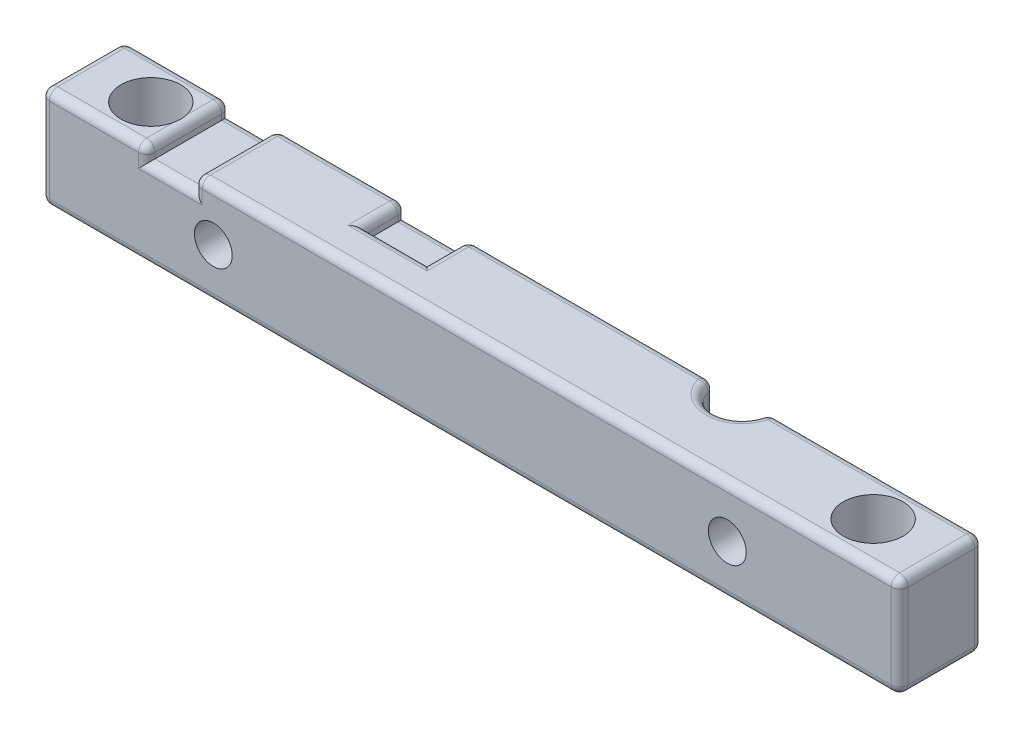
SolidWorks part; units mm, degrees
ref_plane "Front Plane" through (0, 0, 0) normal (0, 0, 1) x (1, 0, 0)
ref_plane "Top Plane" through (0, 0, 0) normal (0, 1, 0) x (1, 0, 0)
ref_plane "Right Plane" through (0, 0, 0) normal (1, 0, 0) x (0, 0, -1)
sketch "Sketch2" plane through (0, 0, 0) normal (0, 1, 0) x (1, 0, 0)
  line L0 (39.243, 7.62) -> (39.243, 0) construction
  line L1 (0, 7.62) -> (78.486, 7.62)
  line L2 (0, 7.62) -> (0, 0)
  line L3 (0, 0) -> (78.486, 0)
  line L4 (78.486, 7.62) -> (78.486, 0)
  line L5 (6.223, 3.81) -> (72.263, 3.81) construction
  circle A0 centre (6.223, 3.81) radius 2.7305
  circle A1 centre (72.263, 3.81) radius 2.7305
  point P10 (39.243, 3.81)
  dimension "D4" = 5.461
  dimension "D1" = 7.62
  dimension "D2" = 78.486
  dimension "D3" = 66.04
extrude "Boss-Extrude1" add sketch "Sketch2" along normal blind 9.271
sketch "Sketch3" plane through (0, 0, 0) normal (0, 0, 1) x (1, 0, 0)
  line L0 (39.243, 9.271) -> (39.243, 0) construction
  line L1 (15.748, 4.6355) -> (62.738, 4.6355) construction
  line L2 (0, 9.271) -> (78.486, 9.271) construction
  line L3 (0, 0) -> (78.486, 0) construction
  circle A0 centre (15.748, 4.6355) radius 1.7272
  circle A1 centre (62.738, 4.6355) radius 1.7272
  point P8 (39.243, 4.6355)
  dimension "D1" = 3.4544
  dimension "D2" = 46.99
extrude "Cut-Extrude1" cut sketch "Sketch3" against normal up to surface (7.62 mm away) up to face at (39.243, 4.6355, -7.62)
sketch "Sketch4" plane through (0, 0, 0) normal (0, -1, 0) x (1, 0, 0)
  line L0 (58.928, -7.7089) -> (53.848, -7.7089)
  line L1 (72.263, -3.81) -> (56.388, -3.81) construction
  line L2 (56.388, -3.81) -> (56.388, -7.7089) construction
  line L3 (78.486, -7.62) -> (0, -7.62) construction
  arc A0 (58.928, -7.7089) -> (53.848, -7.7089) centre (56.388, -7.7089) ccw
  circle A1 centre (72.263, -3.81) radius 2.7305 construction
  dimension "D3" = 2.54
  dimension "D1" = 15.875
  dimension "D2" = 3.8989
extrude "Cut-Extrude2" cut sketch "Sketch4" against normal up to surface (9.271 mm away) up to face at (6.223, 9.271, -1.0795)
sketch "Sketch5" plane through (0, 9.271, 0) normal (0, 1, 0) x (1, 0, 0)
  line L0 (53.8496, 7.62) -> (0, 7.62) construction
  line L1 (13.97, 0) -> (9.652, 0)
  line L2 (13.97, 0) -> (13.97, 7.62)
  line L3 (13.97, 7.62) -> (9.652, 7.62)
  line L4 (9.652, 0) -> (9.652, 7.62)
  line L5 (0, 0) -> (78.486, 0) construction
  line L6 (0, 7.62) -> (0, 0) construction
  line L7 (25.7505, 5.715) -> (28.608, 5.715) construction
  line L8 (25.7505, 7.62) -> (31.4655, 7.62)
  line L9 (25.7505, 7.62) -> (25.7505, 3.81)
  line L10 (25.7505, 3.81) -> (31.4655, 3.81)
  line L11 (31.4655, 7.62) -> (31.4655, 3.81)
  line L12 (28.608, 5.715) -> (28.608, 7.62) construction
  circle A0 centre (6.223, 3.81) radius 2.7305 construction
  dimension "D1" = 3.429
  dimension "D2" = 4.318
  dimension "D3" = 22.385
  dimension "D4" = 5.715
  dimension "D5" = 3.81
extrude "Cut-Extrude3" cut sketch "Sketch5" against normal blind 1.27
fillet "Fillet1" radius 0.762 35 edges at (0, 4.6355, -7.62) (0, 4.6355, 0) (0, 0, -3.81) (26.9248, 0, -7.62) (68.7062, 0, -7.62) (39.243, 0, 0) (78.486, 0, -3.81) (78.486, 4.6355, -7.62) (78.486, 4.6355, 0) (78.486, 9.271, -3.81) (4.826, 9.271, -7.62) (68.7062, 9.271, -7.62) (0, 9.271, -3.81) (46.228, 9.271, 0) (4.826, 9.271, 0) (42.6575, 9.271, -7.62) (58.9264, 4.6355, -7.62) (53.8496, 4.6355, -7.62) (56.388, 0, -5.1689) (56.388, 9.271, -5.1689) (31.4655, 9.271, -5.715) (28.608, 9.271, -3.81) (25.7505, 9.271, -5.715) (13.97, 9.271, -3.81) (9.652, 9.271, -3.81) (28.608, 8.001, -7.62) (11.811, 8.001, 0) (11.811, 8.001, -7.62) (31.4655, 8.636, -7.62) (25.7505, 8.636, -7.62) (13.97, 8.636, -7.62) (9.652, 8.636, -7.62) (19.8603, 9.271, -7.62) (13.97, 8.636, 0) (9.652, 8.636, 0)
